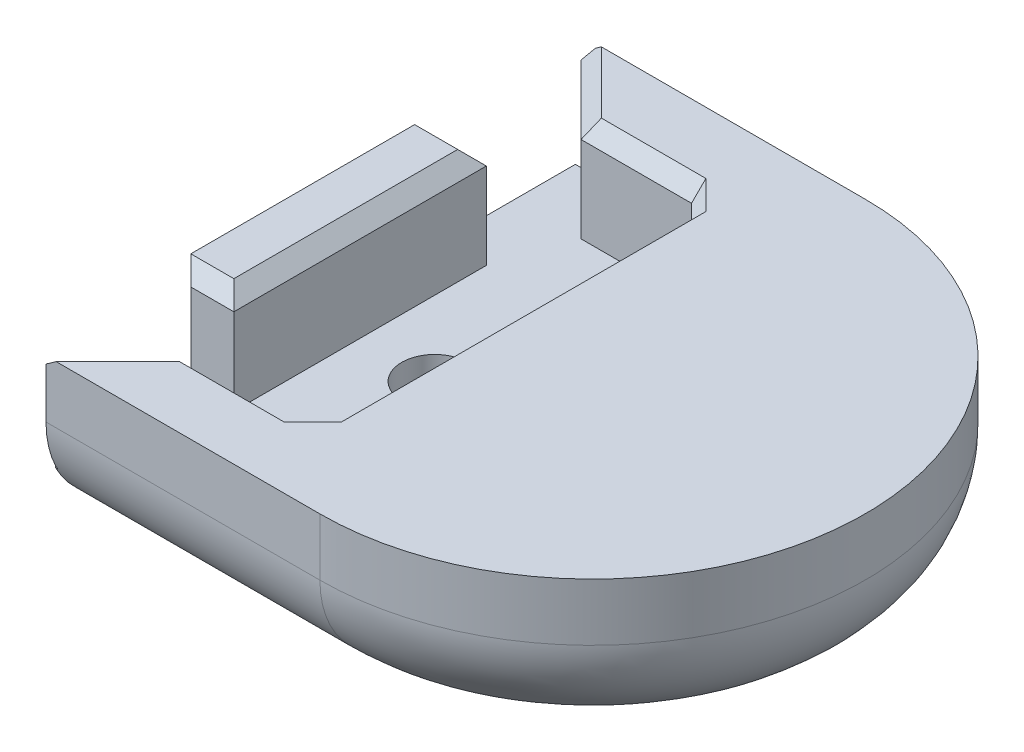
SolidWorks part; units mm, degrees
other "Markup1"
sketch "Sketch13" plane through (9.5, -5.9248, 9.5) normal (0.1837, -0.9341, 0.306) x (0.0497, 0.3198, 0.9462)
ref_plane "Front Plane" through (0, 0, 0) normal (0, 0, 1) x (1, 0, 0)
ref_plane "Top Plane" through (0, 0, 0) normal (0, 1, 0) x (1, 0, 0)
ref_plane "Right Plane" through (0, 0, 0) normal (1, 0, 0) x (0, 0, -1)
sketch "Sketch1" plane through (0, 0, 0) normal (0, 1, 0) x (1, 0, 0)
  line L0 (0, 0) -> (8099.319, 0) construction
  line L1 (0, 0) -> (0, 8099.319) construction
  line L2 (-10.1, -4.5) -> (-10.1, 4.5)
  line L3 (0, 9.5) -> (-10.1, 9.5)
  line L4 (-10.1, 9.5) -> (-10.1, 4.5)
  line L5 (0, -9.5) -> (-10.1, -9.5)
  line L6 (-10.1, -9.5) -> (-10.1, -4.5)
  line L7 (0, 0) -> (9.5, 0) construction
  arc A0 (0, -9.5) -> (0, 9.5) centre (0, 0) ccw
  arc A1 (-8.6, 4.0361) -> (-9.5, 0) centre (0, 0) ccw construction
  arc A2 (-9.5, 0) -> (-8.6, -4.0361) centre (0, 0) ccw construction
  arc A3 (-8.6, -4.0361) -> (0, -9.5) centre (0, 0) ccw construction
  arc A4 (0, 9.5) -> (-8.6, 4.0361) centre (0, 0) ccw construction
  point P8 (-10.1, 0)
  dimension "D2" = 19
  dimension "D1" = 9
  dimension "D3" = 19.6
extrude "Boss-Extrude1" add sketch "Sketch1" against normal blind 2
sketch "Sketch2" plane through (0, 0, 0) normal (0, 1, 0) x (1, 0, 0)
  line L0 (-10.1, 9.5) -> (-10.1, -9.5) construction
  line L1 (-10.1, 4.4) -> (-8.1, 4.4)
  line L2 (-10.1, 4.4) -> (-10.1, 0)
  line L3 (-10.1, 0) -> (-8.1, 0) construction
  line L4 (-8.1, 4.4) -> (-8.1, -4.4)
  line L5 (0, 0) -> (-10.1, 0) construction
  line L6 (-9.9, 9.5) -> (-7.25, 6.85)
  line L7 (-7.25, 6.85) -> (-2.9, 6.85)
  line L8 (-9.9, 9.5) -> (0, 9.5)
  line L10 (-2.9, 6.85) -> (-2.9, -6.85)
  line L11 (-2.9, 0) -> (9.5, 0) construction
  line L12 (-7.25, -6.85) -> (-2.9, -6.85)
  line L13 (-9.9, -9.5) -> (-7.25, -6.85)
  line L14 (-9.9, -9.5) -> (0, -9.5)
  line L15 (-10.1, -4.4) -> (-8.1, -4.4)
  line L16 (-10.1, -4.4) -> (-10.1, 0)
  line L17 (0, 9.5) -> (-10.1, 9.5) construction
  arc A0 (0, -9.5) -> (0, 9.5) centre (0, 0) ccw construction
  arc A1 (0, -9.5) -> (0, 9.5) centre (0, 0) ccw
  dimension "D1" = 4.4
  dimension "D2" = 2
  dimension "D3" = 2.85
  dimension "D4" = 45
  dimension "D5" = 4.35
  dimension "D6" = 0.2
extrude "Boss-Extrude2" add sketch "Sketch2" along normal blind 3.5
sketch "Sketch4" plane through (0, 0, 0) normal (0, 1, 0) x (1, 0, 0)
  line L0 (-8.1, 0) -> (-2.9, 0) construction
  line L1 (-8.1, -4.4) -> (-8.1, 4.4) construction
  line L2 (-2.9, 6.85) -> (-2.9, -6.85) construction
  circle A0 centre (-5.5, 0) radius 1.15
  dimension "D1" = 2.3
extrude "Cut-Extrude1" cut sketch "Sketch4" against normal through all both and the other way through all
ref_plane "Plane2" through (-10.1, 3.5, 4.4) normal (0, 0, 1) x (1, 0, 0)
sketch "Sketch14" plane through (0, -2, 0) normal (0, -1, 0) x (1, 0, 0)
  line L0 (-6.6547, 2) -> (-4.3453, 2)
  line L1 (-4.3453, 2) -> (-3.1906, 0)
  line L2 (-3.1906, 0) -> (-4.3453, -2)
  line L3 (-4.3453, -2) -> (-6.6547, -2)
  line L4 (-6.6547, -2) -> (-7.8094, 0)
  line L5 (-7.8094, 0) -> (-6.6547, 2)
  circle A0 centre (-5.5, 0) radius 2.3094 construction
  dimension "D1" = 4
extrude "Cut-Extrude2" cut sketch "Sketch14" against normal blind 1
chamfer "Chamfer1" distance 0.5 angle 45 24 edges at (-9.1, 3.5, -4.4) (-8.1, 3.5, 0) (-9.1, 3.5, 4.4) (-8.575, 3.5, 8.175) (-5.075, 3.5, 6.85) (-2.9, 3.5, 0) (-5.075, 3.5, -6.85) (-8.575, 3.5, -8.175) (-2.9, 1.75, 6.85) (-2.9, 1.75, -6.85) (-10.1, 0, 6.95) (-10, 0, 9.5) (-9.9, 1.75, 9.5) (-10, 0, -9.5) (-10.1, 0, -6.95) (-9.9, 1.75, -9.5) (-7.2321, -2, -1) (-5.5, -2, -2) (-3.7679, -2, -1) (-3.7679, -2, 1) (-5.5, -2, 2) (-7.2321, -2, 1) (-10.1, 1.75, -4.4) (-10.1, 1.75, 4.4)
fillet "Fillet1" radius 3.5 3 edges at (-5.05, -2, 9.5) (-5.05, -2, -9.5) (9.5, -2, 0)
chamfer "Chamfer2" distance 0.5 angle 45 3 edges at (-10.1, -1.6024, -7.6202) (-10.1, -1.6024, 7.6202) (-10.1, -2, 0)
